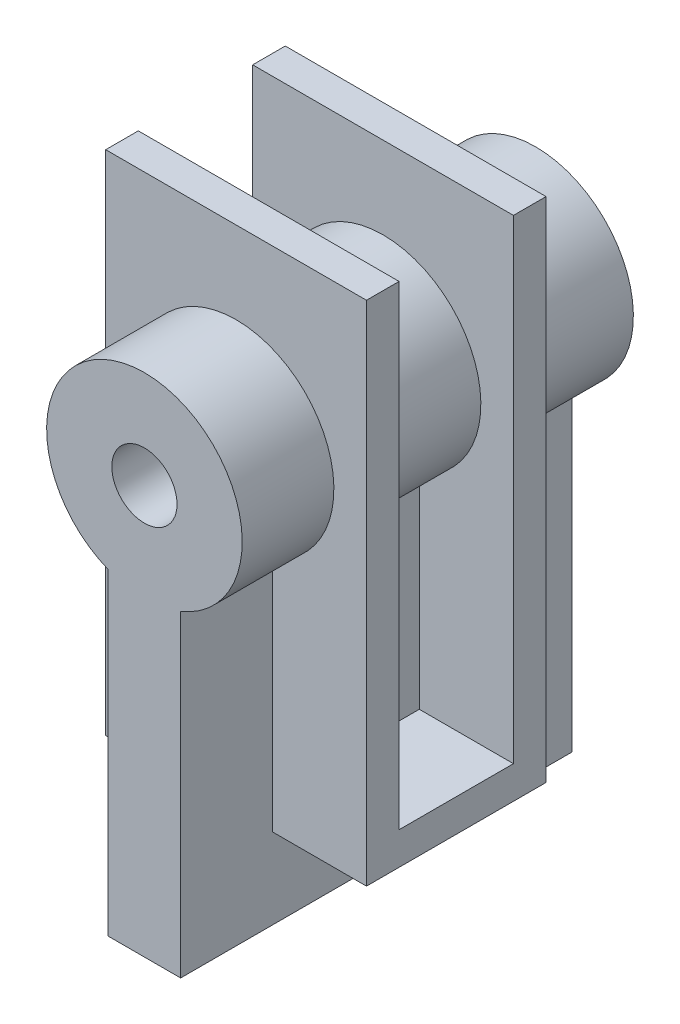
SolidWorks part; units mm, degrees
ref_plane "Спереди" through (0, 0, 0) normal (0, 0, 1) x (1, 0, 0)
ref_plane "Сверху" through (0, 0, 0) normal (0, 1, 0) x (1, 0, 0)
ref_plane "Справа" through (0, 0, 0) normal (1, 0, 0) x (0, 0, -1)
sketch "Эскиз1_fr" plane through (0, 0, 0) normal (0, 0, 1) x (1, 0, 0)
  line L2 (-5.5576, -13.9324) -> (-5.5576, -62.6423)
  line L3 (-5.5576, -62.6423) -> (5.5576, -62.6423)
  line L4 (5.5576, -13.9324) -> (5.5576, -62.6423)
  circle A0 centre (0, 0) radius 5
  arc A1 (5.5576, -13.9324) -> (-5.5576, -13.9324) centre (0, 0) ccw
  circle A3 centre (0, 0) radius 15 construction
  point P9 (14.3446, 4.3856)
  dimension "D1" = 10
  dimension "D2" = 30
sketch "Эскиз3" plane through (0, 0, 0) normal (1, 0, 0) x (0, 0, -1)
  line L0 (-58.3945, -50.2531) -> (-85.9381, -50.2531)
  line L1 (-85.9381, -50.2531) -> (-85.9381, 27.5805)
  line L2 (-58.3945, -50.2531) -> (-58.3945, 27.5805)
  line L3 (-80.9381, -45.2531) -> (-80.9381, 27.5805)
  line L4 (-63.3945, -45.2531) -> (-80.9381, -45.2531)
  line L5 (-63.3945, -45.2531) -> (-63.3945, 27.5805)
  line L6 (-85.9381, 27.5805) -> (-80.9381, 27.5805)
  line L7 (-63.3945, 27.5805) -> (-58.3945, 27.5805)
  point P3 (-72.1663, -50.2531)
extrude "Бобышка-Вытянуть5" add sketch "Эскиз1_fr" along normal blind 30 and the other way blind 30
extrude "Бобышка-Вытянуть6" add sketch "Эскиз3" along normal blind 20 and the other way blind 20 separate body
move or copy body "Тело-Переместить/Копировать1" bodies to move or copy 114 copy no translate (0, 0, -70)
combine bodies "Соединить1" operation type add bodies to combine 112 115
